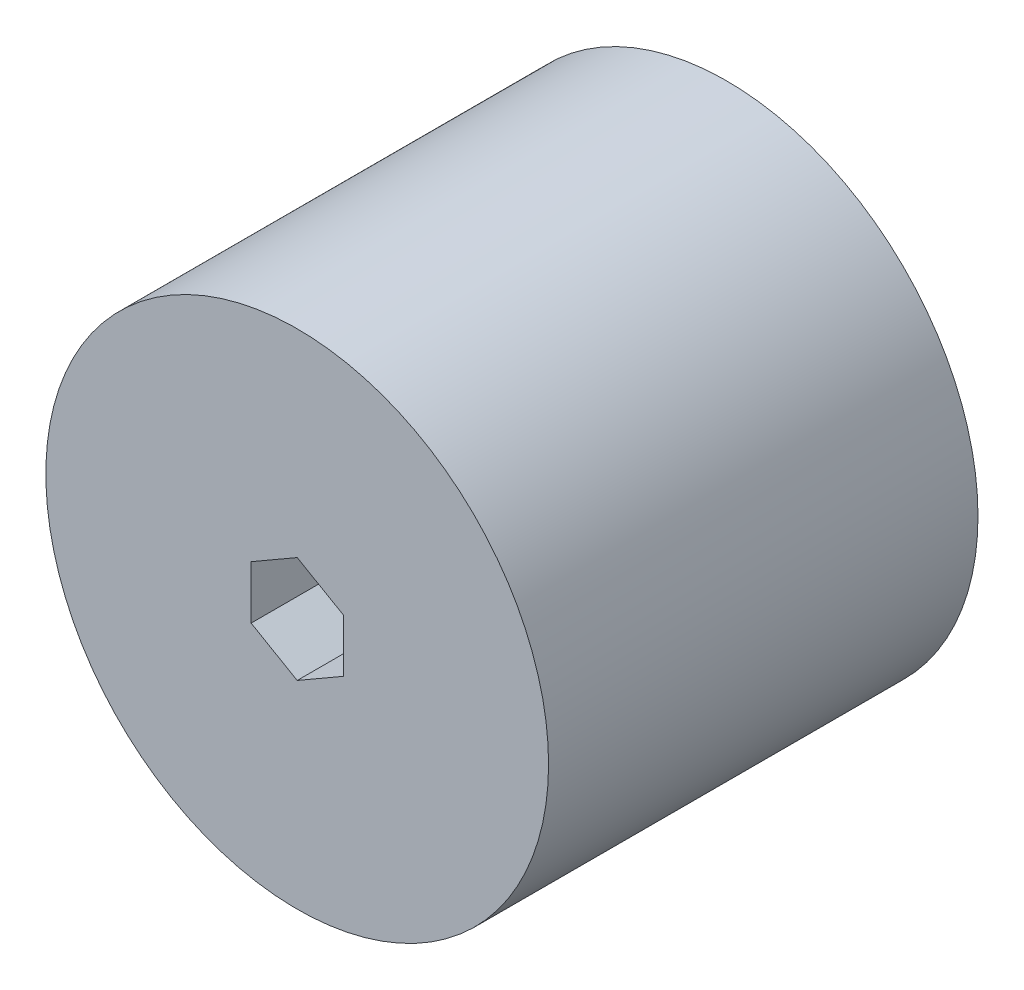
SolidWorks part; units mm, degrees
material "PET"
ref_plane "Front Plane" through (0, 0, 0) normal (0, 0, 1) x (1, 0, 0)
ref_plane "Top Plane" through (0, 0, 0) normal (0, 1, 0) x (1, 0, 0)
ref_plane "Right Plane" through (0, 0, 0) normal (1, 0, 0) x (0, 0, -1)
sketch "Sketch1" plane through (0, 0, 0) normal (0, 0, 1) x (1, 0, 0)
  line L1 (0, 8.0656) -> (-6.985, 4.0328)
  line L2 (-6.985, 4.0328) -> (-6.985, -4.0328)
  line L3 (-6.985, -4.0328) -> (0, -8.0656)
  line L4 (0, -8.0656) -> (6.985, -4.0328)
  line L5 (6.985, -4.0328) -> (6.985, 4.0328)
  line L6 (6.985, 4.0328) -> (0, 8.0656)
  circle A0 centre (0, 0) radius 38.1
  circle A1 centre (0, 0) radius 6.985 construction
  dimension "D1" = 76.2
  dimension "D2" = 13.97
extrude "Boss-Extrude1" add sketch "Sketch1" along normal blind 65.0875
